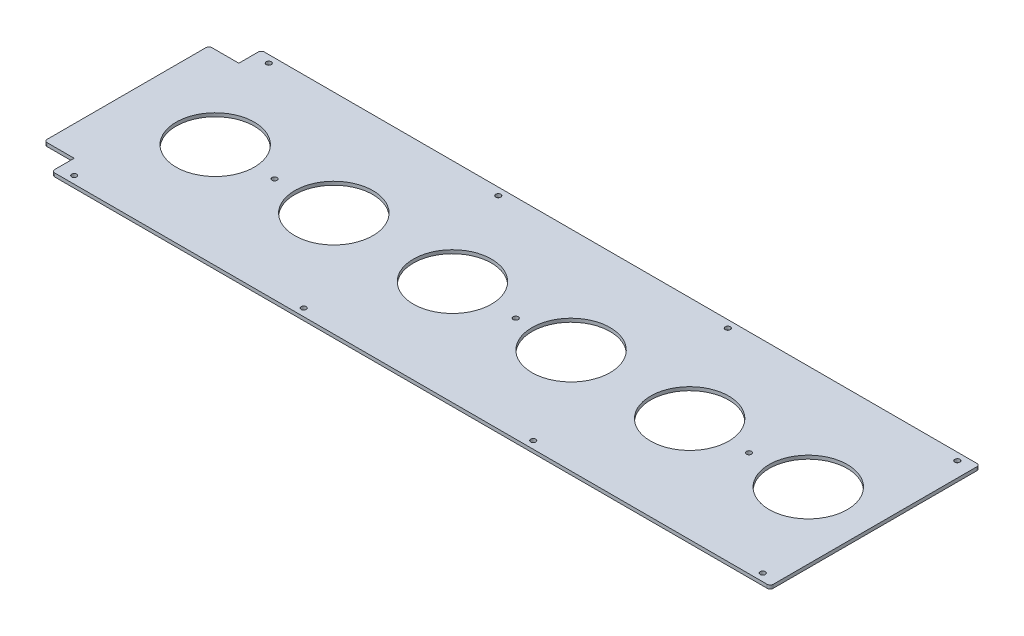
SolidWorks part; units mm, degrees
material "Acrylic (Medium-high impact)"
ref_plane "Front" through (0, 0, 0) normal (0, 0, 1) x (1, 0, 0)
ref_plane "Top" through (0, 0, 0) normal (0, 1, 0) x (1, 0, 0)
ref_plane "Right" through (0, 0, 0) normal (1, 0, 0) x (0, 0, -1)
sketch "Sketch1" plane through (0, 0, 0) normal (0, 1, 0) x (1, 0, 0)
  line L0 (1355.9397, -43.6078) -> (720.9397, -43.6078) construction
  line L5 (1355.9397, 24.9722) -> (1355.9397, -112.1878) construction
  line L6 (720.9397, -112.1878) -> (720.9397, 24.9722) construction
  line L12 (1354.6697, -113.4578) -> (722.2097, -113.4578) construction
  line L13 (746.3397, 45.2922) -> (1355.9397, 45.2922) construction
  line L27 (720.9397, 26.2422) -> (720.9397, -113.4578)
  line L32 (746.3397, -132.5078) -> (1355.9397, -132.5078) construction
  line L44 (1355.9397, 45.2922) -> (1355.9397, -132.5078)
  line L45 (746.3397, 45.2922) -> (1355.9397, -132.5078) construction
  line L50 (746.3397, -132.5078) -> (1355.9397, 45.2922) construction
  line L53 (720.9397, -113.4578) -> (746.3397, -113.4578)
  line L54 (746.3397, -132.5078) -> (746.3397, -113.4578)
  line L58 (720.9397, 26.2422) -> (746.3397, 26.2422)
  line L59 (746.3397, 45.2922) -> (746.3397, 26.2422)
  line L60 (722.2097, 26.2422) -> (1354.6697, 26.2422) construction
  line L61 (1355.9397, -132.5078) -> (746.3397, -132.5078)
  line L62 (1355.9397, 45.2922) -> (746.3397, 45.2922)
  circle A0 centre (1299.3357, -43.6078) radius 33.147
  circle A1 centre (1198.7009, -43.6078) radius 33.147
  circle A2 centre (1098.0661, -43.6078) radius 33.147
  circle A3 centre (997.4313, -43.6078) radius 33.147
  circle A4 centre (896.7965, -43.6078) radius 33.147
  circle A5 centre (796.1617, -43.6078) radius 33.147
  circle A6 centre (1299.3357, -43.6078) radius 33.02 construction
  point P6 (1051.1397, -43.6078)
  dimension "D3" = 0.127
  dimension "D1" = 177.8
  dimension "D2" = 25.4
extrude "Boss-Extrude1" add sketch "Sketch1" along normal blind 2.9718
hole_wizard "#8 Clearance Hole1" positions "Sketch2" profile "Sketch3" hole size "#8" standard "ANSI Inch" end condition through all
sketch "Sketch2" plane through (0, 2.9718, 0) normal (0, 1, 0) x (1, 0, 0)
  point P0 (759.0397, 38.9422)
  point P3 (759.0397, -126.1578)
  point P6 (953.773, -126.1578)
  point P9 (953.773, 38.9422)
  point P12 (1148.5063, 38.9422)
  point P15 (1148.5063, -126.1578)
  point P18 (1343.2397, -126.1578)
  point P22 (1343.2397, 38.9422)
  point P26 (1249.0183, -43.6078)
  point P29 (1051.1397, -43.6078)
  point P32 (846.4791, -43.6078)
sketch "Sketch3" plane through (759.0397, 2.9718, -38.9422) normal (1, 0, 0) x (0, 0, 1)
  line L0 (0, 0) -> (0, 2.9718)
  line L1 (0, 2.9718) -> (2.1526, 2.9718)
  line L2 (2.1526, 2.9718) -> (2.1526, 0)
  line L5 (2.1526, 0) -> (0, 0)
  line L11 (0, -6.35) -> (0, 107.95) construction
  dimension "Thru Hole Dia." = 4.3053
  dimension "Thru Hole Depth" = 2.9718
fillet "Fillet1" radius 2.54 6 edges at (720.9397, 1.4859, 113.4578) (720.9397, 1.4859, -26.2422) (746.3397, 1.4859, -45.2922) (746.3397, 1.4859, 132.5078) (1355.9397, 1.4859, 132.5078) (1355.9397, 1.4859, -45.2922)
